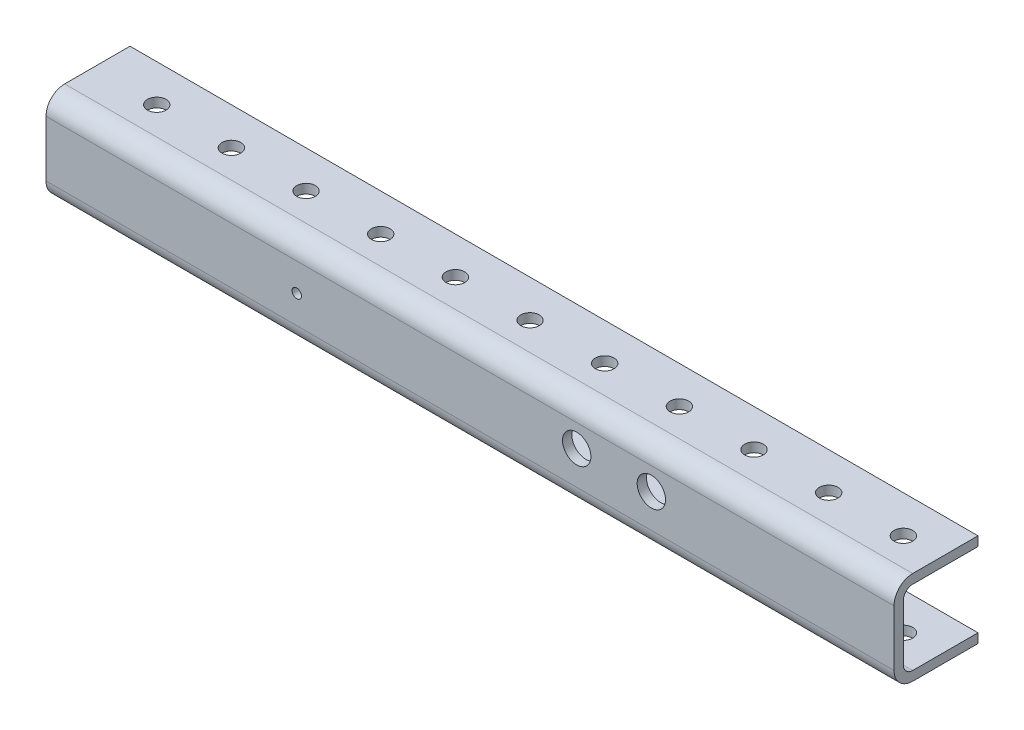
SolidWorks part; units mm, degrees
material "5052-O, Rod (SS)"
ref_plane "Front Plane" through (0, 0, 0) normal (0, 0, 1) x (1, 0, 0)
ref_plane "Top Plane" through (0, 0, 0) normal (0, 1, 0) x (1, 0, 0)
ref_plane "Right Plane" through (0, 0, 0) normal (1, 0, 0) x (0, 0, -1)
ref_plane "Plane1" through (0, 0, 3.175) normal (0, 0, 1) x (1, 0, 0)
sketch "Sketch1" plane through (0, 0, 3.175) normal (0, 0, 1) x (1, 0, 0)
  line L0 (872.98, -7.202) -> (872.98, 24.548)
  line L1 (872.98, 24.548) -> (-16.02, 24.548)
  line L2 (-16.02, 24.548) -> (-16.02, -7.202)
  line L3 (-16.02, -7.202) -> (872.98, -7.202)
extrude "Extrude1" add sketch "Sketch1" against normal blind 28.575
sketch "Sketch2" plane through (-16.02, 0, 0) normal (-1, 0, 0) x (0, 0, 1)
  line L0 (-25.4, 21.373) -> (-25.4, -4.027)
  line L1 (-25.4, -4.027) -> (0, -4.027)
  line L2 (0, -4.027) -> (0, 21.373)
  line L3 (0, 21.373) -> (-25.4, 21.373)
extrude "Extrude2" cut sketch "Sketch2" against normal up to next
hole_wizard "Hole1" positions "Sketch4" profile "Sketch3" legacy
sketch "Sketch4" plane through (0, 24.548, 0) normal (0, 1, 0) x (-1, 0, 0)
  point P0 (3.32, -12.7)
sketch "Sketch3" plane through (-3.32, 24.548, -12.7) normal (1, 0, 0) x (0, 0, 1)
  line L0 (0, 0) -> (0, 3.175)
  line L1 (0, 3.175) -> (3.175, 3.175)
  line L2 (3.175, 3.175) -> (3.175, 0)
  line L3 (3.175, 0) -> (0, 0)
  line L4 (0, 110) -> (0, -10) construction
  dimension "Diameter" = 6.35
  dimension "Depth" = 3.175
sketch3d "3DSketch1"
  point P0 (428.6664, 8.6668, -7.2024)
  point P1 (528.6664, 8.6668, -7.2024)
ref_axis "Axis1" through (528.6664, 8.6668, -7.2024) along (-1, 0, 0)
pattern_linear "LPattern1" count 35 spacing 25.4 along (1, 0, 0) of "Hole1"
hole_wizard "Hole2" positions "Sketch6" profile "Sketch5" legacy
sketch "Sketch6" plane through (0, 0, 3.175) normal (0, 0, 1) x (1, 0, 0)
  point P0 (66.53, 10.578)
sketch "Sketch5" plane through (66.53, 10.578, 3.175) normal (1, 0, 0) x (0, -1, 0)
  line L0 (0, 0) -> (0, 3.175)
  line L1 (0, 3.175) -> (4.826, 3.175)
  line L2 (4.826, 3.175) -> (4.826, 0)
  line L3 (4.826, 0) -> (0, 0)
  line L4 (0, 110) -> (0, -10) construction
  dimension "Diameter" = 9.652
  dimension "Depth" = 3.175
sketch3d "3DSketch2"
  point P0 (428.8468, 8.4517, -7.1294)
  point P1 (528.8468, 8.4517, -7.1294)
ref_axis "Axis2" through (528.8468, 8.4517, -7.1294) along (-1, 0, 0)
pattern_linear "LPattern2" count 12 spacing 25.4 along (1, 0, 0) skipping (2, 0), (3, 0), (4, 0), (5, 0), (6, 0), (7, 0), (8, 0), (9, 0) of "Hole2"
hole_wizard "Hole3" positions "Sketch8" profile "Sketch7" legacy
sketch "Sketch8" plane through (0, 0, 3.175) normal (0, 0, 1) x (1, 0, 0)
  point P0 (428.48, 6.768)
sketch "Sketch7" plane through (428.48, 6.768, 3.175) normal (1, 0, 0) x (0, -1, 0)
  line L0 (0, 0) -> (0, 3.175)
  line L1 (0, 3.175) -> (4.826, 3.175)
  line L2 (4.826, 3.175) -> (4.826, 0)
  line L3 (4.826, 0) -> (0, 0)
  line L4 (0, 110) -> (0, -10) construction
  dimension "Diameter" = 9.652
  dimension "Depth" = 3.175
hole_wizard "Hole4" positions "Sketch10" profile "Sketch9" legacy
sketch "Sketch10" plane through (0, 0, 3.175) normal (0, 0, 1) x (1, 0, 0)
  point P0 (511.03, 10.578)
sketch "Sketch9" plane through (511.03, 10.578, 3.175) normal (1, 0, 0) x (0, -1, 0)
  line L0 (0, 0) -> (0, 3.175)
  line L1 (0, 3.175) -> (4.826, 3.175)
  line L2 (4.826, 3.175) -> (4.826, 0)
  line L3 (4.826, 0) -> (0, 0)
  line L4 (0, 110) -> (0, -10) construction
  dimension "Diameter" = 9.652
  dimension "Depth" = 3.175
sketch3d "3DSketch3"
  point P0 (429.3014, 8.4448, -7.1738)
  point P1 (529.3014, 8.4448, -7.1738)
ref_axis "Axis3" through (529.3014, 8.4448, -7.1738) along (-1, 0, 0)
pattern_linear "LPattern3" count 12 spacing 25.4 along (1, 0, 0) skipping (2, 0), (3, 0), (4, 0), (5, 0), (6, 0), (7, 0), (8, 0), (9, 0) of "Hole4"
hole_wizard "Hole5" positions "Sketch12" profile "Sketch11" legacy
sketch "Sketch12" plane through (0, 0, 3.175) normal (0, 0, 1) x (1, 0, 0)
  point P0 (669.78, 8.673)
sketch "Sketch11" plane through (669.78, 8.673, 3.175) normal (1, 0, 0) x (0, -1, 0)
  line L0 (0, 0) -> (0, 3.175)
  line L1 (0, 3.175) -> (1.5875, 3.175)
  line L2 (1.5875, 3.175) -> (1.5875, 0)
  line L3 (1.5875, 0) -> (0, 0)
  line L4 (0, 110) -> (0, -10) construction
  dimension "Diameter" = 3.175
  dimension "Depth" = 3.175
hole_wizard "Hole6" positions "Sketch14" profile "Sketch13" legacy
sketch "Sketch14" plane through (0, -4.027, 0) normal (0, 1, 0) x (-1, 0, 0)
  point P0 (3.32, -12.7)
sketch "Sketch13" plane through (-3.32, -4.027, -12.7) normal (1, 0, 0) x (0, 0, 1)
  line L0 (0, 0) -> (0, 3.175)
  line L1 (0, 3.175) -> (3.175, 3.175)
  line L2 (3.175, 3.175) -> (3.175, 0)
  line L3 (3.175, 0) -> (0, 0)
  line L4 (0, 110) -> (0, -10) construction
  dimension "Diameter" = 6.35
  dimension "Depth" = 3.175
sketch3d "3DSketch4"
  point P0 (428.6444, 8.4444, -7.1991)
  point P1 (528.6444, 8.4444, -7.1991)
ref_axis "Axis4" through (528.6444, 8.4444, -7.1991) along (-1, 0, 0)
pattern_linear "LPattern4" count 35 spacing 25.4 along (1, 0, 0) of "Hole6"
fillet "Fillet1" radius 3.175 1 edges at (428.48, 21.373, 0) tangent propagation no
fillet "Fillet2" radius 3.175 1 edges at (428.48, -4.027, 0) tangent propagation no
fillet "Fillet3" radius 6.35 1 edges at (428.48, -7.202, 3.175) tangent propagation no
fillet "Fillet4" radius 6.35 1 edges at (428.48, 24.548, 3.175) tangent propagation no
ref_plane "Plane2" through (872.98, 24.548, -3.175) normal (1, 0, 0) x (0, 0, -1)
sketch "Sketch16" plane through (0, 24.548, 0) normal (0, 1, 0) x (1, 0, 0)
  line L0 (112.98, 3.175) -> (112.98, 25.4) construction
  line L1 (-16.02, 3.175) -> (872.98, 3.175) construction
  line L2 (872.98, 25.4) -> (-16.02, 25.4) construction
  line L3 (872.98, 25.4) -> (872.98, 3.175) construction
  line L6 (112.98, 3.175) -> (112.98, 25.4)
  line L7 (112.98, 25.4) -> (-16.02, 25.4)
  line L9 (112.98, 25.4) -> (-32.7801, 25.4)
  line L10 (112.98, 25.4) -> (112.98, -46.1048)
  line L11 (112.98, -46.1048) -> (-32.7801, -46.1048)
  line L12 (-32.7801, 25.4) -> (-32.7801, -46.1048)
  dimension "D1" = 760
extrude "Cut-Extrude2" cut sketch "Sketch16" against normal blind 75 contours L10 L11 L12 L9
sketch "Sketch17" plane through (0, 24.548, 0) normal (0, 1, 0) x (1, 0, 0)
  line L0 (524.98, 3.175) -> (524.98, 25.4) construction
  line L1 (112.98, 3.175) -> (872.98, 3.175) construction
  line L2 (872.98, 25.4) -> (112.98, 25.4) construction
  line L3 (872.98, 25.4) -> (872.98, 3.175) construction
  line L5 (524.98, 25.4) -> (51.3514, 25.4)
  line L6 (524.98, 25.4) -> (524.98, -41.5089)
  line L7 (524.98, -41.5089) -> (51.3514, -41.5089)
  line L8 (51.3514, 25.4) -> (51.3514, -41.5089)
  dimension "D1" = 348
extrude "Cut-Extrude3" cut sketch "Sketch17" against normal blind 186
sketch "Sketch18" plane through (0, 0, 3.175) normal (0, 0, 1) x (1, 0, 0)
  line L0 (524.98, 2.8566) -> (584.48, 2.8566) construction
  line L1 (524.98, -0.852) -> (524.98, 18.198) construction
  line L3 (508.9253, 42.7045) -> (584.48, 42.7045)
  line L4 (508.9253, 42.7045) -> (508.9253, -36.9913)
  line L5 (508.9253, -36.9913) -> (584.48, -36.9913)
  line L6 (584.48, 42.7045) -> (584.48, -36.9913)
  dimension "D1" = 59.5
extrude "Cut-Extrude4" cut sketch "Sketch18" against normal through all
